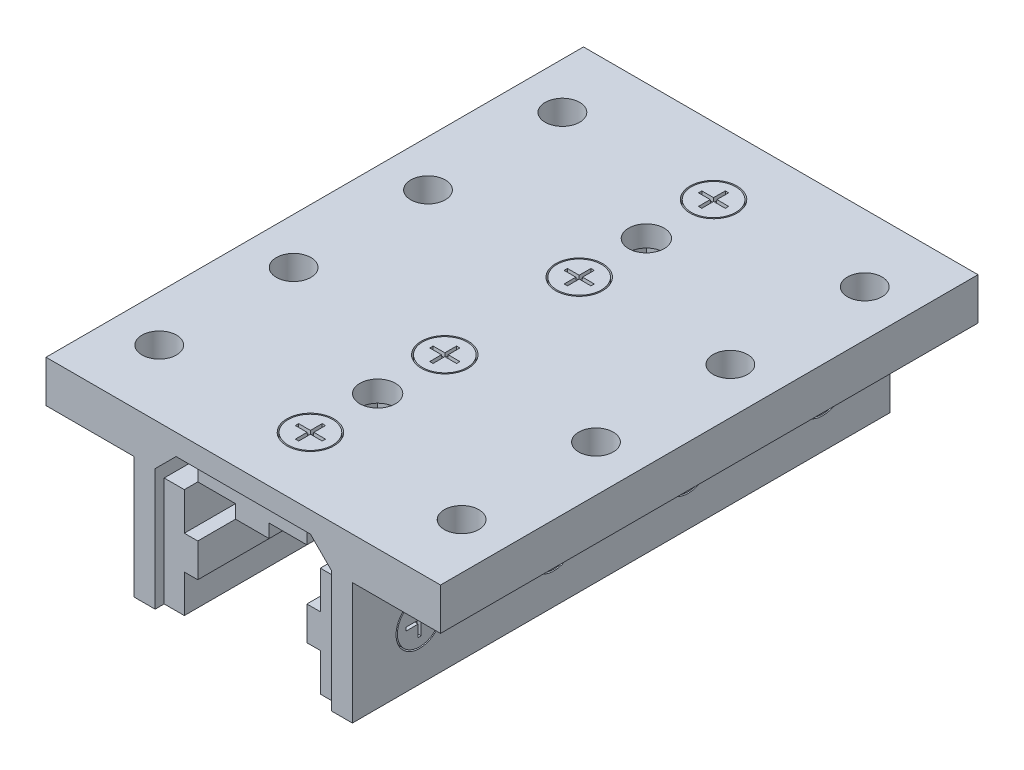
SolidWorks part; units mm, degrees
ref_plane "Front" through (0, 0, 0) normal (0, 0, 1) x (1, 0, 0)
ref_plane "Top" through (0, 0, 0) normal (0, 1, 0) x (1, 0, 0)
ref_plane "Right" through (0, 0, 0) normal (1, 0, 0) x (0, 0, -1)
sketch "Sketch1" plane through (0, 0, 0) normal (0, 0, 1) x (1, 0, 0)
  line L0 (-16.6624, 0) -> (-16.6624, 23.0124)
  line L1 (-20.6248, 30.9372) -> (20.6248, 30.9372)
  line L2 (-20.6248, 30.9372) -> (-20.6248, 0)
  line L3 (-20.6248, 0) -> (-16.6624, 0)
  line L4 (20.6248, 30.9372) -> (20.6248, 0)
  line L5 (-16.6624, 23.0124) -> (-12.7, 26.9748)
  line L6 (-12.7, 26.9748) -> (12.7, 26.9748)
  line L7 (12.7, 26.9748) -> (16.6624, 23.0124)
  line L8 (16.6624, 23.0124) -> (16.6624, 0)
  line L9 (16.6624, 0) -> (20.6248, 0)
  line L11 (-16.6624, 0) -> (16.6624, 0) construction
  dimension "Oall Ht" = 30.9372
  dimension "Base Wd" = 41.2496
  dimension "D2" = 45
  dimension "Leg Thick" = 3.9624
  dimension "Top Thick" = 3.9624
  dimension "Peak Wd" = 25.4
extrude "Boss-Extrude1" add sketch "Sketch1" along normal mid plane 50.8
sketch "Sketch2" plane through (0, 0, 0) normal (0, 0, 1) x (1, 0, 0)
  line L0 (-12.8524, 13.4874) -> (-12.8524, 20.6248)
  line L1 (-16.6624, 0) -> (-12.8524, 0)
  line L2 (-16.6624, 0) -> (-16.6624, 20.6248)
  line L3 (-16.6624, 20.6248) -> (-12.8524, 20.6248)
  line L4 (-12.8524, 0) -> (-12.8524, 7.1374)
  line L5 (-12.8524, 13.4874) -> (-10.3124, 13.4874)
  line L7 (-12.8524, 7.1374) -> (-10.3124, 7.1374)
  line L8 (-10.3124, 13.4874) -> (-10.3124, 7.1374)
  line L12 (-12.7, 26.9748) -> (12.7, 26.9748) construction
  line L13 (-10.3124, 26.9748) -> (10.3124, 26.9748)
  line L14 (-10.3124, 26.9748) -> (-10.3124, 23.1648)
  line L15 (-10.3124, 23.1648) -> (-3.175, 23.1648)
  line L16 (10.3124, 26.9748) -> (10.3124, 23.1648)
  line L17 (3.175, 23.1648) -> (10.3124, 23.1648)
  line L19 (-3.175, 23.1648) -> (-3.175, 20.6248)
  line L20 (-3.175, 20.6248) -> (3.175, 20.6248)
  line L21 (3.175, 23.1648) -> (3.175, 20.6248)
  point P14 (-10.3124, 10.3124)
  point P28 (0, 26.9748)
  dimension "Pad Wd" = 20.6248
  dimension "Pad Thick 1" = 6.35
  dimension "Pad Thick 2" = 3.81
  dimension "Pad Nose" = 6.35
extrude "Boss-Extrude2" add sketch "Sketch2" along normal mid plane 47.371 separate body
sketch "Sketch11" plane through (-10.3124, 0, 0) normal (1, 0, 0) x (0, 0, -1)
  line L0 (-23.6855, 13.4874) -> (23.6855, 13.4874) construction
  line L1 (-3.175, 13.4874) -> (3.175, 13.4874)
  line L2 (-3.175, 13.4874) -> (-3.175, 7.1374)
  line L3 (-3.175, 7.1374) -> (3.175, 7.1374)
  line L4 (3.175, 13.4874) -> (3.175, 7.1374)
  line L5 (-23.6855, 7.1374) -> (23.6855, 7.1374) construction
  point P8 (0, 13.4874)
extrude "Cut-Extrude5" cut sketch "Sketch11" against normal through all
sketch "Sketch12" plane through (0, 20.6248, 0) normal (0, -1, 0) x (1, 0, 0)
  line L0 (-3.175, 23.6855) -> (-3.175, -23.6855) construction
  line L1 (-3.175, 3.175) -> (3.175, 3.175)
  line L2 (-3.175, 3.175) -> (-3.175, -3.175)
  line L3 (-3.175, -3.175) -> (3.175, -3.175)
  line L4 (3.175, 3.175) -> (3.175, -3.175)
  line L5 (3.175, 23.6855) -> (3.175, -23.6855) construction
  point P8 (-3.175, 0)
extrude "Cut-Extrude6" cut sketch "Sketch12" against normal through all
mirror "Mirror1" about plane through (0, 0, 0) normal (1, 0, 0) of bodies 126 109
sketch "Sketch3" plane through (0, 30.9372, 0) normal (0, 1, 0) x (1, 0, 0)
  line L0 (0, -12.7) -> (0, 12.7) construction
  circle A0 centre (0, -12.7) radius 4.445
  circle A1 centre (0, -12.7) radius 4.191
  dimension "D1" = 0.254
  dimension "Screw Head Dia" = 8.89
  dimension "Screw Spacing" = 25.4
extrude "Cut-Extrude1" cut sketch "Sketch3" against normal blind 1.9812
sketch "Sketch5" plane through (0, 30.9372, 0) normal (0, 1, 0) x (1, 0, 0)
  line L0 (0.3175, -12.3825) -> (2.54, -12.3825)
  line L1 (-0.3175, -10.16) -> (0.3175, -10.16)
  line L2 (-0.3175, -10.16) -> (-0.3175, -12.3825)
  line L3 (-0.3175, -15.24) -> (0.3175, -15.24)
  line L4 (0.3175, -10.16) -> (0.3175, -12.3825)
  line L5 (-2.54, -12.3825) -> (-0.3175, -12.3825)
  line L6 (-2.54, -12.3825) -> (-2.54, -13.0175)
  line L7 (-2.54, -13.0175) -> (-0.3175, -13.0175)
  line L8 (2.54, -12.3825) -> (2.54, -13.0175)
  line L9 (-0.3175, -13.0175) -> (-0.3175, -15.24)
  line L10 (0.3175, -13.0175) -> (0.3175, -15.24)
  line L11 (0.3175, -13.0175) -> (2.54, -13.0175)
  line L12 (-0.3175, -12.3825) -> (0.3175, -13.0175) construction
  dimension "D1" = 0.635
  dimension "D2" = 5.08
extrude "Cut-Extrude2" cut sketch "Sketch5" against normal blind 0.762 draft 5
sketch "Sketch13" plane through (20.6248, 0, 0) normal (1, 0, 0) x (0, 0, -1)
  circle A0 centre (-12.7, 10.3124) radius 4.445
  dimension "D1" = 8.89
extrude "Cut-Extrude-Thin1" cut sketch "Sketch13" against normal blind 1.9812 thin thin type one direction reverse wall 0.254
sketch "Sketch14" plane through (20.6248, 0, 0) normal (1, 0, 0) x (0, 0, -1)
  line L0 (-13.0175, 9.9949) -> (-13.0175, 7.7724)
  line L1 (-13.0175, 12.8524) -> (-12.3825, 12.8524)
  line L2 (-13.0175, 12.8524) -> (-13.0175, 10.6299)
  line L3 (-13.0175, 7.7724) -> (-12.3825, 7.7724)
  line L4 (-12.3825, 12.8524) -> (-12.3825, 10.6299)
  line L5 (-15.24, 10.6299) -> (-13.0175, 10.6299)
  line L6 (-15.24, 10.6299) -> (-15.24, 9.9949)
  line L7 (-15.24, 9.9949) -> (-13.0175, 9.9949)
  line L8 (-10.16, 10.6299) -> (-10.16, 9.9949)
  line L9 (-12.3825, 10.6299) -> (-10.16, 10.6299)
  line L10 (-12.3825, 9.9949) -> (-12.3825, 7.7724)
  line L11 (-12.3825, 9.9949) -> (-10.16, 9.9949)
  line L12 (-13.0175, 10.6299) -> (-12.3825, 9.9949) construction
  dimension "D1" = 0.635
  dimension "D2" = 5.08
extrude "Cut-Extrude7" cut sketch "Sketch14" against normal blind 0.762 draft 5
mirror "Mirror4" about plane through (0, 0, 0) normal (1, 0, 0) of "Cut-Extrude7", "Cut-Extrude-Thin1"
mirror "Mirror3" about plane through (0, 0, 0) normal (0, 0, 1) of "Mirror4", "Cut-Extrude-Thin1", "Cut-Extrude7", "Cut-Extrude1", "Cut-Extrude2"
sketch "Sketch9" plane through (0, 30.9372, 0) normal (0, 1, 0) x (1, 0, 0)
  circle A0 centre (0, 0) radius 3.3655
  dimension "Top Hole Dia" = 6.731
extrude "Cut-Extrude4" cut sketch "Sketch9" against normal through all
sketch "Sketch15" plane through (0, 0, 0) normal (1, 0, 0) x (0, 0, -1)
  circle A0 centre (0, 10.3124) radius 3.3655
  dimension "Side Wall Hole Dia" = 6.731
extrude "Cut-Extrude8" cut sketch "Sketch15" against normal through all and the other way through all
sketch "Sketch16" plane through (0, 0, 0) normal (0, 0, 1) x (1, 0, 0)
  line L1 (-37.2872, 30.9372) -> (-18.6436, 30.9372)
  line L2 (-37.2872, 30.9372) -> (-37.2872, 23.0124)
  line L3 (-37.2872, 23.0124) -> (-18.6436, 23.0124)
  line L4 (-18.6436, 30.9372) -> (-18.6436, 23.0124)
  line L5 (20.6248, 30.9372) -> (-20.6248, 30.9372) construction
  line L6 (18.6436, 30.9372) -> (37.2872, 30.9372)
  line L7 (18.6436, 30.9372) -> (18.6436, 23.0124)
  line L8 (18.6436, 23.0124) -> (37.2872, 23.0124)
  line L9 (37.2872, 30.9372) -> (37.2872, 23.0124)
  line L10 (-20.6248, 0) -> (-16.6624, 0) construction
  line L11 (16.6624, 0) -> (20.6248, 0) construction
  point P4 (-18.6436, 0)
  point P13 (18.6436, 0)
  dimension "Oall Wd" = 74.5744
  dimension "Top Flange Thickness" = 7.9248
extrude "Top Flange" add sketch "Sketch16" along normal up to surface (25.4 mm away) and the other way up to surface (25.4 mm away) up to face at (0, 16.1849, 25.4) other way up to face at (0, 16.1849, -25.4)
sketch "Sketch17" plane through (0, 30.9372, 0) normal (0, 1, 0) x (1, 0, 0)
  line L0 (-28.575, 12.7) -> (28.575, -12.7) construction
  line L1 (-28.575, 12.7) -> (28.575, 12.7) construction
  line L2 (-28.575, 12.7) -> (-28.575, -12.7) construction
  line L3 (-28.575, -12.7) -> (28.575, -12.7) construction
  line L4 (28.575, 12.7) -> (28.575, -12.7) construction
  line L5 (-18.6436, 12.7) -> (-20.6248, 12.7) construction
  circle A0 centre (28.575, 12.7) radius 3.2639
  circle A1 centre (28.575, -12.7) radius 3.2639
  circle A2 centre (-28.575, 12.7) radius 3.2639
  circle A3 centre (-28.575, -12.7) radius 3.2639
  dimension "Top Flange Hole Dia" = 6.5278
  dimension "Top Flange Hole Spacing" = 57.15
extrude "Top Flange Hole" cut sketch "Sketch17" against normal through all
mirror "Mirror7" about plane through (-20.6248, 0, -25.4) normal (0, 0, 1) of bodies 126 128 114
mirror "Mirror6" about plane through (-20.6248, 0, -25.4) normal (0, 0, 1) of bodies 135 134
equation "\"D1@Cut-Extrude1\" = \"Top Thick@Sketch1\" * .5"
equation "\"D1@Sketch13\" = \"Screw Head Dia@Sketch3\""
equation "\"D1@Cut-Extrude-Thin1\" = \"Leg Thick@Sketch1\" * .5"
equation "\"D5@Cut-Extrude-Thin1\" = \"D1@Sketch3\""
equation "\"D1@Cut-Extrude7\" = \"D1@Cut-Extrude2\""
equation "\"D1@Sketch14\" = \"D1@Sketch5\""
equation "\"D2@Sketch14\" = \"D2@Sketch5\""
equation "\"D3@Cut-Extrude7\" = \"D3@Cut-Extrude2\""
